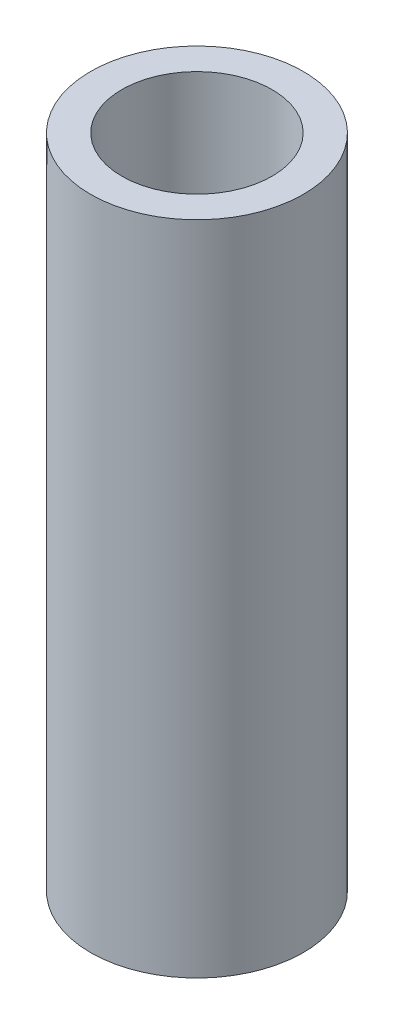
SolidWorks part; units mm, degrees
material "ABS"
ref_plane "Front Plane" through (0, 0, 0) normal (0, 0, 1) x (1, 0, 0)
ref_plane "Top Plane" through (0, 0, 0) normal (0, 1, 0) x (1, 0, 0)
ref_plane "Right Plane" through (0, 0, 0) normal (1, 0, 0) x (0, 0, -1)
sketch "Sketch1" plane through (0, 0, 0) normal (0, 1, 0) x (1, 0, 0)
  circle A0 centre (0, 0) radius 24
  circle A1 centre (0, 0) radius 34
  dimension "D1" = 48
  dimension "D2" = 68
extrude "Boss-Extrude1" add sketch "Sketch1" along normal blind 209.8
sketch "Sketch2" plane through (0, 0, 0) normal (1, 0, 0) x (0, 0, -1)
  line L0 (24, 209.8) -> (-24, 209.8) construction
  circle A0 centre (0, 145.6) radius 12.53
  circle A1 centre (0, 87.6) radius 12.53
  circle A2 centre (0, 29.6) radius 12.53
  dimension "D1" = 25.06
  dimension "D2" = 25.06
  dimension "D3" = 25.06
  dimension "D4" = 64.2
  dimension "D5" = 58
  dimension "D6" = 58
extrude "Cut-Extrude1" cut sketch "Sketch2" against normal through all
